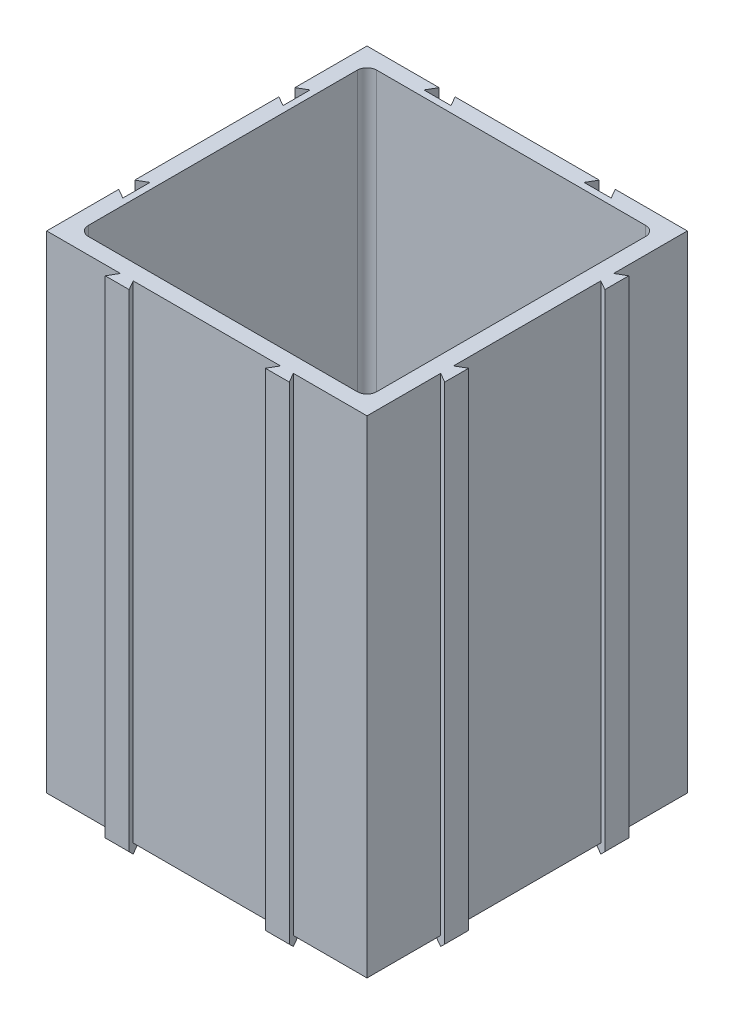
SolidWorks part; units mm, degrees
ref_plane "Front Plane" through (0, 0, 0) normal (0, 0, 1) x (1, 0, 0)
ref_plane "Top Plane" through (0, 0, 0) normal (0, 1, 0) x (1, 0, 0)
ref_plane "Right Plane" through (0, 0, 0) normal (1, 0, 0) x (0, 0, -1)
sketch "Sketch1" plane through (0, 0, 0) normal (0, 1, 0) x (1, 0, 0)
  line L0 (-11, 2.116) -> (-11, -2.116)
  line L3 (0, 16.0204) -> (0, -19.6084) construction
  line L5 (18.0663, 0) -> (-17.4129, 0) construction
  line L6 (-11, -2.116) -> (-12.5, -1.25)
  line L7 (-12.5, -1.25) -> (-12.5, -12.5)
  line L8 (-12.5, 1.25) -> (-12.5, 12.5)
  line L9 (-11, 2.116) -> (-12.5, 1.25)
  line L10 (0, 0) -> (-12.5, 12.5) construction
  line L11 (-2.116, 11) -> (-1.25, 12.5) construction
  line L12 (-1.25, 12.5) -> (-12.5, 12.5) construction
  line L13 (1.25, 12.5) -> (12.5, 12.5) construction
  line L14 (2.116, 11) -> (1.25, 12.5) construction
  line L15 (-2.116, 11) -> (2.116, 11) construction
  line L16 (-12.5, -12.5) -> (-1, -12.5)
  line L17 (-1, -12.5) -> (-1.866, -14)
  line L18 (-1.866, -14) -> (1.866, -14)
  line L19 (1, -12.5) -> (1.866, -14)
  line L20 (12.5, -12.5) -> (1, -12.5)
  line L21 (-16.0204, 0) -> (19.6084, 0) construction
  line L22 (12.5, -12.5) -> (12.5, -1) construction
  line L23 (12.5, -1) -> (14, -1.866) construction
  line L24 (14, 1.866) -> (14, -1.866) construction
  line L25 (12.5, 1) -> (14, 1.866) construction
  line L26 (12.5, 12.5) -> (12.5, 1) construction
  line L27 (-2.116, 21.0883) -> (-2.116, -12.7995) construction
  line L28 (1.25, 18.3402) -> (1.25, -13.7995) construction
  line L29 (-10, 10) -> (-10, -10)
  line L30 (-10, 10) -> (10, 10) construction
  line L31 (-10, -10) -> (10, -10)
  line L32 (10, 10) -> (10, -10) construction
  line L33 (22.884, 11) -> (23.75, 12.5) construction
  line L34 (26.25, 12.5) -> (37.5, 12.5) construction
  line L35 (27.116, 11) -> (26.25, 12.5) construction
  line L36 (22.884, 11) -> (27.116, 11) construction
  line L37 (24, -12.5) -> (23.134, -14)
  line L38 (23.134, -14) -> (26.866, -14)
  line L39 (26, -12.5) -> (26.866, -14)
  line L40 (37.5, -12.5) -> (26, -12.5)
  line L41 (37.5, -12.5) -> (37.5, -1)
  line L42 (37.5, -1) -> (39, -1.866)
  line L43 (39, 1.866) -> (39, -1.866)
  line L44 (37.5, 1) -> (39, 1.866)
  line L45 (37.5, 12.5) -> (37.5, 1)
  line L46 (35, 10) -> (35, -10)
  line L47 (15, 10) -> (35, 10) construction
  line L48 (15, -10) -> (35, -10)
  line L49 (23.75, 12.5) -> (12.5, 12.5) construction
  line L50 (12.5, -12.5) -> (24, -12.5)
  line L51 (15, -10) -> (35, 10) construction
  line L52 (10, 10) -> (15, 10) construction
  line L53 (10, -10) -> (15, -10)
  line L54 (-11, 27.116) -> (-11, 22.884)
  line L55 (-11, 22.884) -> (-12.5, 23.75)
  line L56 (-12.5, 26.25) -> (-12.5, 37.5)
  line L57 (-11, 27.116) -> (-12.5, 26.25)
  line L58 (-2.116, 36) -> (-1.25, 37.5)
  line L59 (-1.25, 37.5) -> (-12.5, 37.5)
  line L60 (1.25, 37.5) -> (12.5, 37.5)
  line L61 (2.116, 36) -> (1.25, 37.5)
  line L62 (-2.116, 36) -> (2.116, 36)
  line L63 (-10, 35) -> (10, 35)
  line L64 (22.884, 36) -> (23.75, 37.5)
  line L65 (26.25, 37.5) -> (37.5, 37.5)
  line L66 (27.116, 36) -> (26.25, 37.5)
  line L67 (22.884, 36) -> (27.116, 36)
  line L68 (37.5, 24) -> (39, 23.134)
  line L69 (39, 26.866) -> (39, 23.134)
  line L70 (37.5, 26) -> (39, 26.866)
  line L71 (37.5, 37.5) -> (37.5, 26)
  line L72 (15, 35) -> (35, 35)
  line L73 (23.75, 37.5) -> (12.5, 37.5)
  line L74 (10, 35) -> (15, 35)
  line L75 (0, 25) -> (-12.5, 37.5) construction
  line L76 (-16.0204, 25) -> (19.6084, 25) construction
  line L77 (37.5, 12.5) -> (37.5, 24)
  line L78 (35, 35) -> (35, 15)
  line L79 (-10, 35) -> (-10, 15)
  line L80 (-12.5, 23.75) -> (-12.5, 12.5)
  line L81 (-10, 15) -> (-10, 10)
  line L82 (35, 15) -> (35, 10)
  point P12 (-11, 0)
  point P13 (0, 11)
  point P23 (0, -14)
  point P31 (14, 0)
  point P39 (25, 0)
  point P40 (-10, 0)
  point P42 (0, -10)
  point P43 (0, 10)
  point P47 (25, 11)
  point P57 (25, -14)
  point P63 (39, 0)
  point P68 (25, -10)
  point P69 (25, 10)
  point P78 (-11, 25)
  point P79 (0, 36)
  point P87 (14, 25)
  point P91 (-10, 25)
  point P92 (0, 35)
  point P94 (25, 36)
  point P105 (39, 25)
  point P109 (25, 35)
  dimension "D1" = 60
  dimension "D2" = 2.5
  dimension "D3" = 25
  dimension "D4" = 1.5
  dimension "D5" = 45
  dimension "D6" = 0.5
  dimension "D7" = 60
  dimension "D8" = 0.5
  dimension "D9" = 20
  dimension "D10" = 2
  dimension "D11" = 25
  dimension "D13" = 25
  dimension "D12" = 2
extrude "Boss-Extrude1" add sketch "Sketch1" along normal blind 77.5 contours L55 L80 L8 L9 L0 L6 L7 L16 L17 L18 L19 L20 L50 L37 L38 L39 L40 L41 L42 L43 L44 L45 L77 L68 L69 L70 L71 L65 L66 L67 L64 L73 L60 L61 L62 L58 L59 L56 L57 L54 L78 L82 L46 L48 L53 L31 L29 L81 L79 L63 region at (-12.1142, 0, -2.3138)
sketch "Sketch2" plane through (0, 0, 0) normal (0, 1, 0) x (1, 0, 0)
  line L12 (-10, 35) -> (-10, -10)
  line L13 (-10, -10) -> (35, -10)
  line L14 (35, -10) -> (35, 35)
  line L15 (35, 35) -> (-10, 35)
  line L16 (-10, 35) -> (-10, -10)
  line L17 (-10, -10) -> (35, -10)
  line L18 (35, -10) -> (35, 35)
  line L19 (35, 35) -> (-10, 35)
  dimension "D1" = 0
extrude "Boss-Extrude2" add sketch "Sketch2" along normal blind 2.5
sketch "Sketch3" plane through (0, 2.5, 0) normal (0, 1, 0) x (1, 0, 0)
  line L0 (0, 14.7677) -> (0, 0) construction
  line L1 (0, 0) -> (-17.9797, 0) construction
  line L2 (0, 0) -> (-14.7542, 14.7542) construction
  line L3 (12.5, 37.5) -> (12.5, 12.5) construction
  line L4 (23.75, 37.5) -> (1.25, 37.5) construction
  line L5 (12.5, 12.5) -> (37.5, 12.5) construction
  line L6 (37.5, 24) -> (37.5, 1) construction
  circle A0 centre (-6, 6) radius 1.5
  circle A1 centre (6, 6) radius 1.5
  circle A2 centre (6, -6) radius 1.5
  circle A3 centre (-6, -6) radius 1.5
  circle A4 centre (31, -6) radius 1.5
  circle A5 centre (19, -6) radius 1.5
  circle A6 centre (19, 6) radius 1.5
  circle A7 centre (31, 6) radius 1.5
  circle A8 centre (31, 19) radius 1.5
  circle A9 centre (19, 19) radius 1.5
  circle A10 centre (19, 31) radius 1.5
  circle A11 centre (31, 31) radius 1.5
  circle A12 centre (-6, 31) radius 1.5
  circle A13 centre (6, 31) radius 1.5
  circle A14 centre (6, 19) radius 1.5
  circle A15 centre (-6, 19) radius 1.5
  point P17 (37.5, 12.5)
  dimension "D3" = 3
  dimension "D1" = 45
  dimension "D2" = 6
extrude "Cut-Extrude1" cut sketch "Sketch3" against normal through all both and the other way through all
chamfer "Chamfer3" distance 1.5 angle 45 20 edges at (39, 0, -25) (0, 0, 14) (25, 0, 14) (39, 0, 0) (-11, 0, 0) (-11, 0, -25) (0, 0, -36) (25, 0, -36) (-12.5, 0, -12.5) (-12.5, 0, 6.875) (-6.75, 0, 12.5) (12.5, 0, 12.5) (31.75, 0, 12.5) (37.5, 0, 6.75) (37.5, 0, -12.5) (-12.5, 0, -31.875) (-6.875, 0, -37.5) (12.5, 0, -37.5) (37.5, 0, -31.75) (31.875, 0, -37.5)
chamfer "Chamfer2" distance 1 angle 45 20 edges at (12.5, 2.5, 10) (-10, 2.5, -12.5) (-6, 2.5, -4.5) (6, 2.5, -4.5) (6, 2.5, 7.5) (-6, 2.5, 7.5) (35, 2.5, -12.5) (12.5, 2.5, -35) (-6, 2.5, -29.5) (31, 2.5, -29.5) (19, 2.5, -29.5) (19, 2.5, -17.5) (6, 2.5, -29.5) (6, 2.5, -17.5) (-6, 2.5, -17.5) (31, 2.5, 7.5) (19, 2.5, 7.5) (19, 2.5, -4.5) (31, 2.5, -4.5) (31, 2.5, -17.5)
fillet "Fillet1" radius 1.5 4 edges at (-10, 40.5, 10) (35, 40.5, 10) (35, 40.5, -35) (-10, 40.5, -35)
